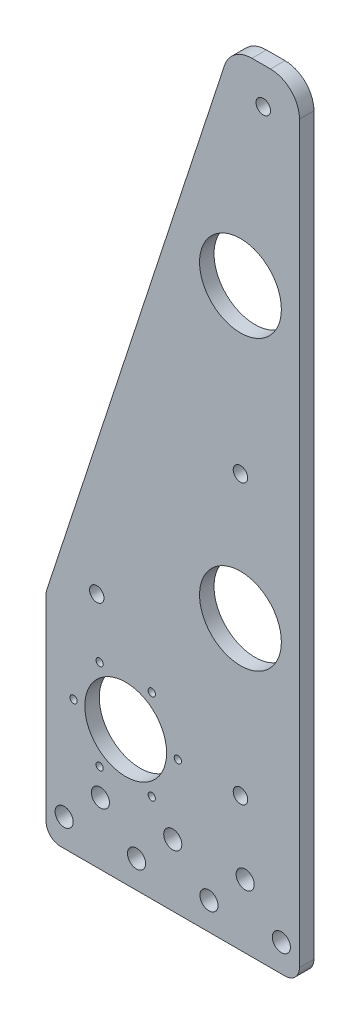
SolidWorks part; units mm, degrees
material "PC High Viscosity"
ref_plane "Front Plane" through (0, 0, 0) normal (0, 0, 1) x (1, 0, 0)
ref_plane "Top Plane" through (0, 0, 0) normal (0, 1, 0) x (1, 0, 0)
ref_plane "Right Plane" through (0, 0, 0) normal (1, 0, 0) x (0, 0, -1)
sketch "Sketch1" plane through (0, 0, 0) normal (0, 0, 1) x (1, 0, 0)
  line L2 (88.9, 212.09) -> (88.9, 5.08)
  line L3 (83.82, 0) -> (5.08, 0)
  line L4 (78.74, 222.25) -> (55.6253, 222.25)
  line L5 (45.9692, 215.25) -> (0.252, 75.55)
  line L6 (0, 73.97) -> (0, 5.08)
  line L7 (6.35, 9.652) -> (31.75, 9.652) construction
  line L8 (27.94, 46.99) -> (27.94, 82.7405) construction
  line L9 (27.94, 46.99) -> (60.7143, 46.99) construction
  circle A0 centre (68.199, 201.93) radius 14.351
  circle A1 centre (68.199, 100.838) radius 14.351
  circle A2 centre (68.199, 144.78) radius 2.54
  circle A3 centre (68.199, 46.99) radius 2.54
  arc A4 (78.74, 222.25) -> (88.9, 212.09) centre (78.74, 212.09) cw
  arc A5 (0, 5.08) -> (5.08, 0) centre (5.08, 5.08) ccw
  arc A6 (88.9, 5.08) -> (83.82, 0) centre (83.82, 5.08) cw
  arc A7 (55.6253, 222.25) -> (45.9692, 215.25) centre (55.6253, 212.09) ccw
  arc A8 (0.252, 75.55) -> (0, 73.97) centre (5.08, 73.97) ccw
  circle A9 centre (27.94, 46.99) radius 14.351
  circle A17 centre (68.199, 201.93) radius 50.8 construction
  circle A18 centre (68.199, 100.838) radius 38.1 construction
  circle A19 centre (6.35, 9.652) radius 3.175
  circle A21 centre (31.75, 9.652) radius 3.175
  circle A22 centre (57.15, 9.652) radius 3.175
  circle A23 centre (82.55, 9.652) radius 3.175
  circle A29 centre (69.85, 22.352) radius 3.175
  circle A30 centre (44.45, 21.844) radius 3.175
  circle A31 centre (19.05, 21.844) radius 3.175
  circle A32 centre (46.228, 46.99) radius 1.27
  circle A38 centre (37.084, 31.1521) radius 1.27
  circle A39 centre (18.796, 31.1521) radius 1.27
  circle A40 centre (9.652, 46.99) radius 1.27
  circle A41 centre (18.796, 62.8279) radius 1.27
  circle A42 centre (37.084, 62.8279) radius 1.27
  point P17 (88.9, 222.25)
  point P20 (0, 0)
  point P23 (88.9, 0)
  point P25 (48.26, 222.25)
  point P26 (48.26, 222.25)
  point P43 (27.94, 46.99)
  point P69 (27.94, 46.99)
  dimension "D1" = 28.702
  dimension "D2" = 28.702
  dimension "D4" = 88.9
  dimension "D7" = 5.08
  dimension "D9" = 5.08
  dimension "D11" = 10.16
  dimension "D12" = 5.08
  dimension "D13" = 10.16
  dimension "D14" = 5.08
  dimension "D16" = 28.702
  dimension "D17" = 18.288
  dimension "D23" = 139.7
  dimension "D24" = 101.6
  dimension "D25" = 76.2
  dimension "D26" = 6.35
  dimension "D29" = 21.844
  dimension "D31" = 6.35
  dimension "D32" = 4
  dimension "D34" = 19.05
  dimension "D39" = 21.844
  dimension "D30" = 6.35
  dimension "D35" = 6.35
  dimension "D37" = 6.35
  dimension "D38" = 25.4
  dimension "D18" = 2.54
  dimension "D3" = 101.092
  dimension ".75" = 20.701
  dimension "D5" = 222.25
  dimension "D6" = 20.32
  dimension "D8" = 57.15
  dimension "D10" = 97.79
  dimension "D15" = 40.64
  dimension "D20" = 27.94
  dimension "D21" = 9.144
  dimension "D22" = 15.8379
  dimension "D27" = 9.652
  dimension "D28" = 25.4
  dimension "D33" = 12.7
  dimension "D36" = 25.4
  dimension "D19" = 6
extrude "Boss-Extrude1" add sketch "Sketch1" along normal blind 5.08
sketch "Sketch2" plane through (0, 0, 5.08) normal (0, 0, 1) x (1, 0, 0)
  line L0 (45.9692, 215.25) -> (62.5937, 266.05)
  line L1 (45.9692, 215.25) -> (0.252, 75.55) construction
  line L2 (72.2498, 273.05) -> (78.74, 273.05)
  line L3 (88.9, 262.89) -> (88.9, 212.09)
  line L4 (78.74, 222.25) -> (55.6253, 222.25) construction
  line L5 (45.9692, 215.25) -> (55.6253, 222.25)
  line L6 (55.6253, 222.25) -> (78.74, 222.25)
  line L7 (78.74, 222.25) -> (88.9, 212.09)
  line L8 (76.2, 156.304) -> (76.2, 48.354) construction
  line L9 (88.9, 5.08) -> (88.9, 212.09) construction
  arc A0 (78.74, 273.05) -> (88.9, 262.89) centre (78.74, 262.89) cw
  arc A1 (62.5937, 266.05) -> (72.2498, 273.05) centre (72.2498, 262.89) cw
  circle A2 centre (76.2, 260.35) radius 2.54
  point P19 (68.199, 144.78)
  dimension "D2" = 10.16
  dimension "D3" = 5.08
  dimension "D1" = 50.8
  dimension "D4" = 12.7
  dimension "D5" = 12.7
extrude "Boss-Extrude2" add sketch "Sketch2" against normal blind 5.08
sketch "Sketch3" plane through (0, 0, 5.08) normal (0, 0, 1) x (1, 0, 0)
  line L0 (68.199, 83.058) -> (-39.9215, 83.058) construction
  line L1 (17.78, 46.99) -> (17.78, -14.087) construction
  circle A1 centre (17.78, 83.058) radius 2.54
  point P0 (68.199, 100.838)
  point P2 (27.94, 46.99)
  dimension "D1" = 5.08
  dimension "D2" = 10.16
  dimension "D3" = 17.78
extrude "Cut-Extrude1" cut sketch "Sketch3" against normal through all contours A1
